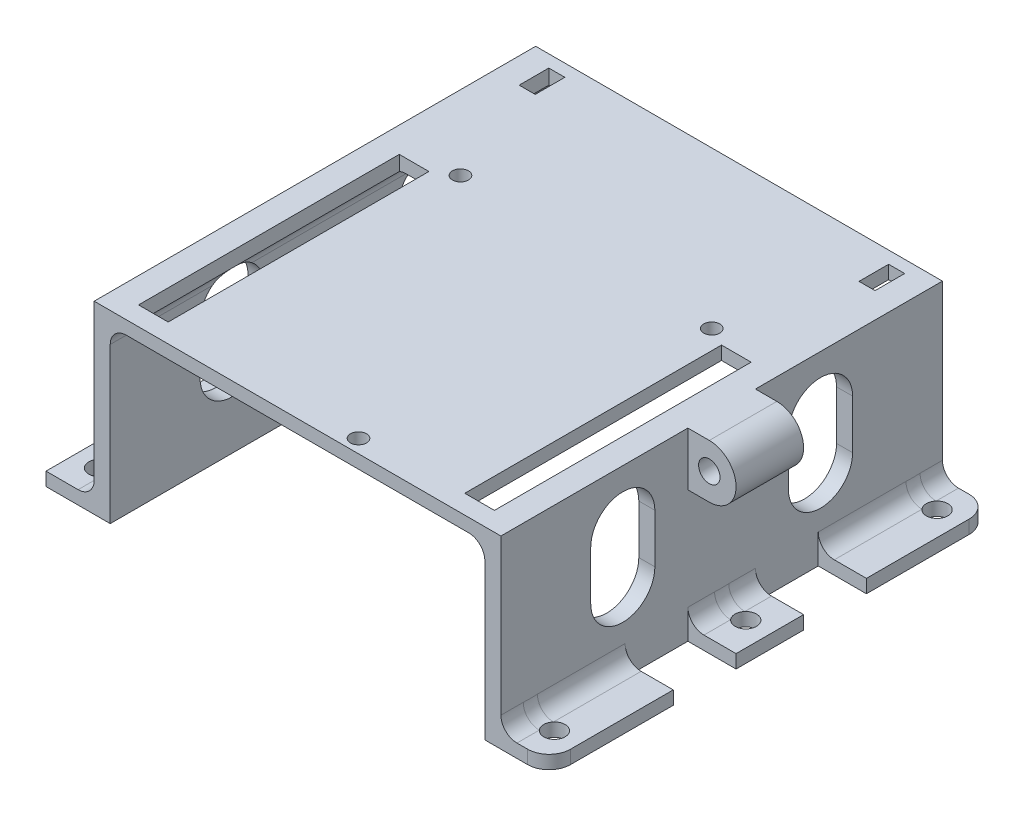
SolidWorks part; units mm, degrees
ref_plane "Front Plane" through (0, 0, 0) normal (0, 0, 1) x (1, 0, 0)
ref_plane "Top Plane" through (0, 0, 0) normal (0, 1, 0) x (1, 0, 0)
ref_plane "Right Plane" through (0, 0, 0) normal (1, 0, 0) x (0, 0, -1)
sketch "Sketch1" plane through (0, 0, 0) normal (0, 1, 0) x (1, 0, 0)
  line L0 (-35, 41.25) -> (-38, 41.25)
  line L1 (-35, -41.25) -> (35, -41.25)
  line L2 (-35, -41.25) -> (-35, 41.25)
  line L3 (-35, 41.25) -> (35, 41.25)
  line L4 (35, -41.25) -> (35, 41.25)
  line L5 (-35, -41.25) -> (35, 41.25) construction
  line L6 (-35, 41.25) -> (35, -41.25) construction
  line L7 (-38, 41.25) -> (-38, -41.25)
  line L8 (-38, -41.25) -> (-35, -41.25)
  line L9 (-38, -41.25) -> (-47, -41.25)
  line L10 (-47, -41.25) -> (-47, 41.25)
  line L11 (-47, 41.25) -> (-38, 41.25)
  line L12 (0, 21.0903) -> (0, -28.1695) construction
  line L13 (47, 41.25) -> (38, 41.25)
  line L14 (47, -41.25) -> (47, 41.25)
  line L15 (38, -41.25) -> (47, -41.25)
  line L16 (38, 41.25) -> (38, -41.25)
  line L17 (38, -41.25) -> (35, -41.25)
  line L18 (35, 41.25) -> (38, 41.25)
  line L19 (-42.5, 41.25) -> (-42.5, -41.25) construction
  line L20 (42.5, 41.25) -> (42.5, -41.25) construction
  line L21 (-58.5063, 0) -> (72.588, 0) construction
  circle A0 centre (-42.5, 35.75) radius 2
  circle A1 centre (-42.5, -35.75) radius 2
  circle A2 centre (42.5, -35.75) radius 2
  circle A3 centre (42.5, 35.75) radius 2
  circle A4 centre (-42.5, 0) radius 2
  circle A5 centre (42.5, 0) radius 2
  point P0 (0, 0)
  dimension "D3" = 4
  dimension "D4" = 4
  dimension "D5" = 5.5
  dimension "D9" = 4
  dimension "D10" = 4
  dimension "D1" = 3
  dimension "D2" = 9
  dimension "D6" = 5.5
  dimension "D7" = 82.5
  dimension "D8" = 70
extrude "Boss-Extrude1" add sketch "Sketch1" along normal blind 2.5 contours L11 L10 L9 L7 A1 A0 | L13 L16 L15 L14 A2 A3 region at (-38.8299, 0, 0) region at (42.5, 0, -40.4201)
extrude "Boss-Extrude2" add sketch "Sketch1<3>" along normal blind 32 contours L7 L8 L2 L0 | L18 L4 L17 L16 region at (-36.5, 0, 0) region at (36.5, 0, 0)
sketch "Sketch1<3>" plane through (0, 0, 0) normal (0, 1, 0) x (1, 0, 0) same geometry as "Sketch1"
extrude "Boss-Extrude3" add sketch "Sketch1<5>" along normal blind 2.5 from surface contours L7 L8 L2 L0 | L18 L4 L17 L16 | L1 L4 L3 L2 region at (-36.5, 0, 0) region at (0, 0, 0) region at (36.5, 0, 0) starting at face at (-36.5, 32, 0)
sketch "Sketch1<5>" plane through (0, 0, 0) normal (0, 1, 0) x (1, 0, 0) same geometry as "Sketch1"
fillet "Fillet1" radius 3 2 edges at (35, 32, 0) (-35, 32, 0)
fillet "Fillet2" radius 4 2 edges at (47, 1.25, 41.25) (47, 1.25, -41.25)
sketch "Sketch2" plane through (0, 2.5, 0) normal (0, 1, 0) x (1, 0, 0)
  line L0 (-42.5, 0) -> (42.5, 0) construction
  line L1 (48.0101, 18.0465) -> (38, 18.0465)
  line L2 (38, -41.25) -> (38, 41.25) construction
  line L3 (38, 18.0465) -> (38, 6.3106)
  line L4 (38, 6.3106) -> (48.0101, 6.3106)
  line L5 (48.0101, 6.3106) -> (48.0101, 18.0465)
  line L6 (48.0101, -6.3106) -> (48.0101, -18.0465)
  line L7 (38, -6.3106) -> (48.0101, -6.3106)
  line L8 (38, -18.0465) -> (38, -6.3106)
  line L9 (48.0101, -18.0465) -> (38, -18.0465)
extrude "Cut-Extrude1" cut sketch "Sketch2" against normal through all both and the other way through all
fillet "Fillet4" radius 3 4 edges at (-38, 2.5, 0) (38, 2.5, 29.6482) (38, 2.5, 0) (38, 2.5, -29.6482)
sketch "Sketch3" plane through (-38, 0, 0) normal (-1, 0, 0) x (0, 0, 1)
  line L0 (18.4733, 15.128) -> (18.4733, 24.2824) construction
  line L1 (12.4833, 15.128) -> (12.4833, 24.2824)
  line L2 (24.4633, 15.128) -> (24.4633, 24.2824)
  line L3 (0, 7.6501) -> (0, 29.8023) construction
  line L4 (-18.4733, 15.128) -> (-18.4733, 24.2824) construction
  line L5 (-12.4833, 15.128) -> (-12.4833, 24.2824)
  line L6 (-24.4633, 15.128) -> (-24.4633, 24.2824)
  arc A0 (12.4833, 15.128) -> (24.4633, 15.128) centre (18.4733, 15.128) ccw
  arc A1 (24.4633, 24.2824) -> (12.4833, 24.2824) centre (18.4733, 24.2824) ccw
  arc A2 (-12.4833, 15.128) -> (-24.4633, 15.128) centre (-18.4733, 15.128) cw
  arc A3 (-24.4633, 24.2824) -> (-12.4833, 24.2824) centre (-18.4733, 24.2824) cw
  point P2 (18.4733, 19.7052)
  point P12 (-18.4733, 19.7052)
extrude "Cut-Extrude2" cut sketch "Sketch3" against normal through all both and the other way through all
sketch "Sketch4" plane through (0, 34.5, 0) normal (0, 1, 0) x (1, 0, 0)
  line L0 (-38, -41.25) -> (-38, 41.25) construction
  line L1 (38, -41.25) -> (-38, -41.25) construction
  line L2 (-31.75, -36.21) -> (-29.21, -36.21) construction
  line L3 (-31.75, -36.21) -> (-31.75, 9.51) construction
  line L4 (-31.75, 9.51) -> (-29.21, 9.51) construction
  line L5 (-29.21, -36.21) -> (-29.21, 9.51) construction
  line L6 (29.21, -36.21) -> (31.75, -36.21) construction
  line L7 (29.21, -36.21) -> (29.21, 9.51) construction
  line L8 (29.21, 9.51) -> (31.75, 9.51) construction
  line L9 (31.75, -36.21) -> (31.75, 9.51) construction
  line L10 (-31.75, 34.91) -> (-31.75, 37.45) construction
  line L11 (-33.25, -37.71) -> (-27.71, -37.71)
  line L12 (-33.25, -37.71) -> (-33.25, 11.01)
  line L13 (-33.25, 11.01) -> (-27.71, 11.01)
  line L14 (-27.71, -37.71) -> (-27.71, 11.01)
  line L15 (27.71, -37.71) -> (33.25, -37.71)
  line L16 (27.71, -37.71) -> (27.71, 10.26)
  line L17 (27.71, 10.26) -> (33.25, 10.26)
  line L18 (33.25, -37.71) -> (33.25, 10.26)
  line L19 (31.75, 34.91) -> (31.75, 37.45) construction
  line L21 (-31.75, 37.45) -> (31.75, 37.45) construction
  line L23 (-33.25, 33.41) -> (-30.25, 33.41)
  line L24 (-33.25, 33.41) -> (-33.25, 38.95)
  line L25 (-33.25, 38.95) -> (-30.25, 38.95)
  line L26 (-30.25, 33.41) -> (-30.25, 38.95)
  line L27 (30.25, 33.41) -> (33.25, 33.41)
  line L28 (30.25, 33.41) -> (30.25, 38.95)
  line L29 (30.25, 38.95) -> (33.25, 38.95)
  line L30 (33.25, 33.41) -> (33.25, 38.95)
  circle A0 centre (-24.13, 13.32) radius 1.5
  circle A1 centre (24.13, 12.03) radius 1.5
  circle A2 centre (8.89, -38.75) radius 1.5
  point P30 (-30.48, -36.21)
  dimension "D1" = 3
  dimension "D2" = 2.54
  dimension "D3" = 3
  dimension "D4" = 3
  dimension "D5" = 46.89
  dimension "D6" = 5.04
  dimension "D7" = 2.54
  dimension "D8" = 2.54
  dimension "D9" = 45.72
  dimension "D10" = 3.81
  dimension "D11" = 7.62
  dimension "D12" = 48.26
  dimension "D13" = 63.5
  dimension "D14" = 6.25
  dimension "D15" = 48.24
  dimension "D16" = 1.5
  dimension "D17" = 1.5
  dimension "D18" = 1.5
  dimension "D19" = 1.5
  dimension "D20" = 1.5
  dimension "D21" = 1.5
  dimension "D22" = 1.5
  dimension "D23" = 1.5
  dimension "D24" = 2.54
  dimension "D25" = 71.12
  dimension "D26" = 1.5
  dimension "D27" = 1.5
  dimension "D28" = 1.5
  dimension "D29" = 1.5
  dimension "D30" = 1.5
  dimension "D31" = 1.5
  dimension "D32" = 1.5
  dimension "D33" = 1.5
extrude "Cut-Extrude3" cut sketch "Sketch4" against normal through all both and the other way through all
sketch "Sketch5" plane through (0, 0, 0) normal (0, 0, 1) x (1, 0, 0)
  line L1 (38, 34.5) -> (42, 34.5)
  line L2 (42, 24.5) -> (38, 24.5)
  line L3 (38, 34.5) -> (38, 5.5) construction
  line L4 (38, 34.5) -> (38, 24.5)
  arc A0 (42, 34.5) -> (42, 24.5) centre (42, 29.5) cw
  circle A1 centre (42, 29.5) radius 2
  dimension "D1" = 4
  dimension "D2" = 5
  dimension "D3" = 4
extrude "Boss-Extrude4" add sketch "Sketch5" along normal up to surface and the other way up to surface contours A0 L1 L4 L2 A1 region at (40, 34.3655, 0) up to face at (42.0757, 1.9757, 6.3106) other way up to face at (42.0757, 1.9757, -6.3106)
